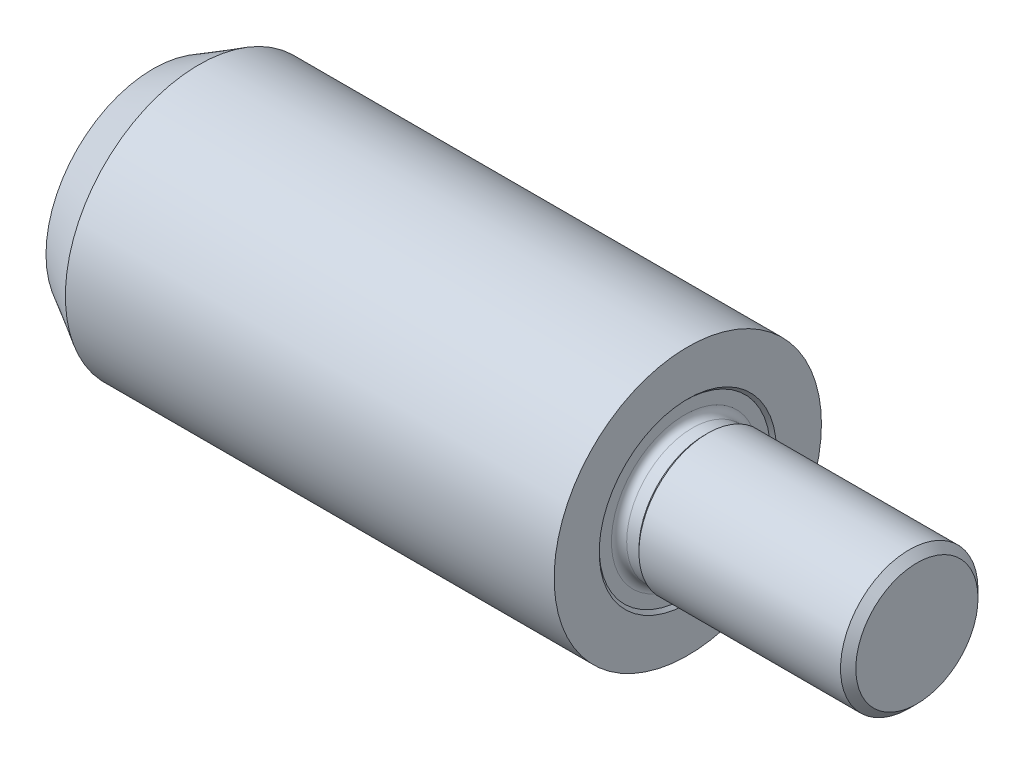
SolidWorks part; units mm, degrees
ref_plane "前视基准面" through (0, 0, 0) normal (0, 0, 1) x (1, 0, 0)
ref_plane "上视基准面" through (0, 0, 0) normal (0, 1, 0) x (1, 0, 0)
ref_plane "右视基准面" through (0, 0, 0) normal (1, 0, 0) x (0, 0, -1)
sketch "草图3" plane through (0, 0, 0) normal (0, 0, 1) x (1, 0, 0)
  line L0 (0, 0) -> (0, 14.0359)
  line L1 (0, -55) -> (0, 55) construction
  line L2 (0, 14.0359) -> (6, 17.5)
  line L3 (6, 17.5) -> (70, 17.5)
  line L4 (70, 17.5) -> (70, 9)
  line L5 (70, 9) -> (100, 9)
  line L6 (100, 9) -> (100, 0)
  line L7 (55, 0) -> (-55, 0) construction
  line L8 (100, 0) -> (0, 0) construction
  line L9 (0, 0) -> (100, 0)
  dimension "D1" = 100
  dimension "D2" = 70
  dimension "D3" = 6
  dimension "D4" = 30
  dimension "D5" = 35
  dimension "D6" = 18
revolve "旋转1" add sketch "草图3" angle 360 about L8
chamfer "倒角1" distance 1 angle 45 1 edges at (100, 0, -9)
sketch "草图4" plane through (0, 0, 0) normal (0, 0, 1) x (1, 0, 0)
  line L0 (66.5005, 0) -> (78.1765, 0) construction
  line L1 (19.25, 0) -> (-19.25, 0) construction
  line L2 (69.6, 11.6) -> (69.6, 8.6)
  line L3 (69.6, 8.6) -> (72.6, 8.6)
  line L4 (99, 9) -> (70, 9) construction
  line L5 (70, -17.5) -> (70, 17.5) construction
  line L7 (69.6, 11.6) -> (72.6, 11.6)
  line L8 (72.6, 11.6) -> (72.6, 8.6)
  dimension "D1" = 3
  dimension "D2" = 3
  dimension "D3" = 0.4
  dimension "D4" = 0.4
revolve "切除-旋转1" cut sketch "草图4" angle 360 about L0
fillet "圆角1" radius 1 1 edges at (69.6, 0, 8.6)
chamfer "倒角2" distance 0.4 angle 45 2 edges at (69.6, 0, 11.6) (72.6, 0, 8.6)
